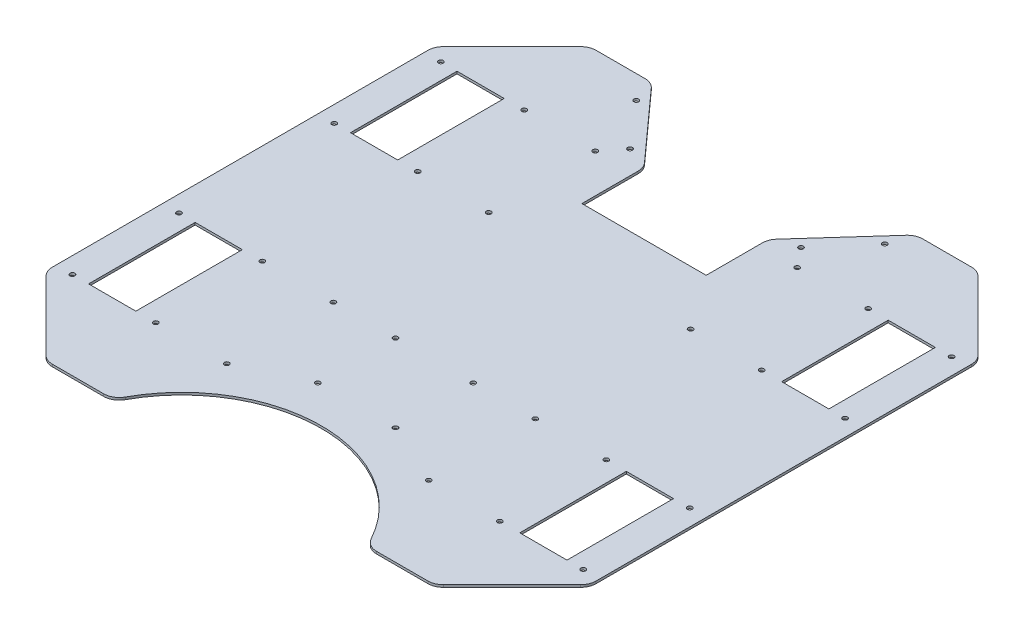
SolidWorks part; units mm, degrees
material "PMMA"
ref_plane "前视基准面" through (0, 0, 0) normal (0, 0, 1) x (1, 0, 0)
ref_plane "上视基准面" through (0, 0, 0) normal (0, 1, 0) x (1, 0, 0)
ref_plane "右视基准面" through (0, 0, 0) normal (1, 0, 0) x (0, 0, -1)
other "Configuration Table"
sketch "草图1" plane through (0, 0, 0) normal (0, 1, 0) x (1, 0, 0)
  line L0 (-125, 175) -> (-175, 125)
  line L1 (125, -175) -> (81.7103, -175)
  line L2 (175, -125) -> (175, 125)
  line L3 (125, 175) -> (85, 175)
  line L4 (-175, -125) -> (-175, 125)
  line L5 (-85, 175) -> (-40, 125)
  line L7 (125, 175) -> (175, 125)
  line L8 (175, -125) -> (125, -175)
  line L9 (-125, -175) -> (-175, -125)
  line L10 (40, 125) -> (85, 175)
  line L11 (-85, 175) -> (-125, 175)
  line L12 (40, 125) -> (40, 85)
  line L13 (40, 85) -> (-40, 85)
  line L14 (-40, 85) -> (-40, 125)
  line L15 (-153.994, 50) -> (-123.594, 50)
  line L16 (-123.594, 50) -> (-123.594, 118.58)
  line L17 (-123.594, 118.58) -> (-153.994, 118.58)
  line L18 (-153.994, 118.58) -> (-153.994, 50)
  line L19 (123.594, 50) -> (153.994, 50)
  line L20 (153.994, 50) -> (153.994, 118.58)
  line L21 (153.994, 118.58) -> (123.594, 118.58)
  line L22 (123.594, 118.58) -> (123.594, 50)
  line L23 (-175, 0) -> (175, 0) construction
  line L24 (-123.594, -118.58) -> (-153.994, -118.58)
  line L25 (-123.594, -50) -> (-123.594, -118.58)
  line L26 (-153.994, -50) -> (-123.594, -50)
  line L27 (-153.994, -118.58) -> (-153.994, -50)
  line L28 (153.994, -118.58) -> (123.594, -118.58)
  line L29 (153.994, -50) -> (153.994, -118.58)
  line L30 (123.594, -50) -> (153.994, -50)
  line L31 (123.594, -118.58) -> (123.594, -50)
  line L32 (-81.7103, -175) -> (-125, -175)
  line L33 (-80, 160) -> (-55, 131) construction
  circle A0 centre (-55, 131) radius 1.55
  circle A1 centre (-80, 160) radius 1.55
  circle A2 centre (55, 131) radius 1.55
  circle A3 centre (80, 160) radius 1.55
  circle A4 centre (-65, 118.58) radius 1.55
  circle A5 centre (-65, 50) radius 1.55
  circle A6 centre (-110.72, 50) radius 1.55
  circle A7 centre (-110.72, 118.58) radius 1.55
  circle A12 centre (-164.434, 118.58) radius 1.55
  circle A13 centre (-164.434, 50) radius 1.55
  circle A14 centre (-65, -118.58) radius 1.55
  circle A15 centre (-65, -50) radius 1.55
  circle A16 centre (-110.72, -50) radius 1.55
  circle A17 centre (-110.72, -118.58) radius 1.55
  circle A18 centre (-164.434, -50) radius 1.55
  circle A19 centre (-164.434, -118.58) radius 1.55
  circle A20 centre (65, 50) radius 1.55
  circle A21 centre (110.72, 50) radius 1.55
  circle A22 centre (110.72, 118.58) radius 1.55
  circle A23 centre (65, 118.58) radius 1.55
  circle A24 centre (164.434, 118.58) radius 1.55
  circle A25 centre (164.434, 50) radius 1.55
  circle A26 centre (164.434, -118.58) radius 1.55
  circle A27 centre (164.434, -50) radius 1.55
  circle A28 centre (110.72, -50) radius 1.55
  circle A29 centre (110.72, -118.58) radius 1.55
  circle A30 centre (65, -118.58) radius 1.55
  circle A31 centre (65, -50) radius 1.55
  arc A32 (-81.7103, -175) -> (81.7103, -175) centre (0, -212.7283) cw
  circle A33 centre (25, -50) radius 1.55
  circle A34 centre (25, -100) radius 1.55
  circle A35 centre (-25, -50) radius 1.55
  circle A36 centre (-25, -100) radius 1.55
  point P0 (0, 0)
  point P1 (-85, 175)
  point P2 (85, 175)
  point P3 (40, 125)
  point P4 (-40, 125)
  point P6 (125, 175)
  point P8 (175, 125)
  point P10 (175, -125)
  point P11 (125, -175)
  point P12 (-125, -175)
  point P13 (-175, -125)
  point P24 (-80, 160)
  point P25 (-55, 131)
  point P26 (55, 131)
  point P27 (80, 160)
  point P36 (-164.434, 118.58)
  point P37 (-164.434, 50)
  point P38 (-153.994, 118.58)
  point P39 (-123.594, 50)
  point P40 (-110.72, 118.58)
  point P41 (-110.72, 50)
  point P42 (-65, 118.58)
  point P43 (-65, 50)
  point P47 (-123.594, 118.58)
  point P53 (-153.994, 50)
  point P66 (-40, 85)
  point P67 (40, 85)
  point P70 (110.72, 50)
  point P71 (65, 50)
  point P72 (123.594, 50)
  point P73 (153.994, 50)
  point P74 (164.434, 50)
  point P75 (65, 118.58)
  point P76 (110.72, 118.58)
  point P77 (123.594, 118.58)
  point P78 (153.994, 118.58)
  point P81 (164.434, 118.58)
  point P85 (-65, -118.58)
  point P88 (-65, -50)
  point P91 (-110.72, -50)
  point P94 (-110.72, -118.58)
  point P101 (-164.434, -50)
  point P104 (-164.434, -118.58)
  point P118 (164.434, -118.58)
  point P121 (164.434, -50)
  point P128 (110.72, -50)
  point P131 (110.72, -118.58)
  point P134 (65, -118.58)
  point P137 (65, -50)
  point P149 (0, 0)
  point P150 (0, 0)
  point P151 (0, 0)
  point P152 (-989.1218, 614.5739)
  point P153 (0, 0)
  point P154 (0, 0)
  dimension "D29" = 3.1
  dimension "D30" = 3.1
  dimension "D31" = 3.1
  dimension "D32" = 3.1
  dimension "D40" = 3.1
  dimension "D41" = 3.1
  dimension "D42" = 3.1
  dimension "D43" = 3.1
  dimension "D44" = 3.1
  dimension "D45" = 3.1
  dimension "D46" = 3.1
  dimension "D47" = 3.1
  dimension "D48" = 3.1
  dimension "D49" = 3.1
  dimension "D60" = 3.1
  dimension "D61" = 3.1
  dimension "D62" = 43.2897
  dimension "D63" = 90
  dimension "D67" = 3.1
  dimension "D68" = 3.1
  dimension "D69" = 3.1
  dimension "D70" = 3.1
  dimension "D1" = 175
  dimension "D2" = 175
  dimension "D3" = 125
  dimension "D4" = 125
  dimension "D5" = 125
  dimension "D6" = 125
  dimension "D7" = 125
  dimension "D8" = 125
  dimension "D9" = 125
  dimension "D10" = 125
  dimension "D11" = 175
  dimension "D12" = 175
  dimension "D13" = 40
  dimension "D14" = 40
  dimension "D15" = 85
  dimension "D16" = 85
  dimension "D17" = 125
  dimension "D18" = 125
  dimension "D19" = 40
  dimension "D20" = 45
  dimension "D21" = 160
  dimension "D22" = 160
  dimension "D23" = 80
  dimension "D24" = 80
  dimension "D25" = 55
  dimension "D26" = 131
  dimension "D27" = 55
  dimension "D28" = 131
  dimension "D33" = 50
  dimension "D34" = 118.58
  dimension "D35" = 65
  dimension "D36" = 45.72
  dimension "D37" = 12.874
  dimension "D38" = 30.4
  dimension "D39" = 10.44
  dimension "D50" = 40
  dimension "D51" = 40
  dimension "D52" = 85
  dimension "D53" = 85
  dimension "D54" = 138.013
  dimension "D55" = 65
  dimension "D56" = 45.72
  dimension "D57" = 12.874
  dimension "D58" = 30.4
  dimension "D59" = 10.44
  dimension "D64" = 0
  dimension "D65" = 25
  dimension "D66" = 25
  dimension "D71" = 50
  dimension "D72" = 50
extrude "凸台-拉伸1" add sketch "草图1" along normal blind 1.5 contours A1 | A0 | L8 L1 A32 L32 L9 L4 L0 L11 L5 L14 L13 L12 L10 L3 L7 L2 | A5 | A3 | A2 | A4 | A7 | A12 | L16 L17 L18 L15 | A6 | L21 L22 L19 L20 | A13 | A16 | A17 | A14 | A15 | A18 | A19 | L25 L24 L27 L26 | A20 | A21 | A22 | A23 | A24 | A25 | A28 | A26 | A27 | L28 L31 L30 L29 | A30 | A31 | A29 | A35 | A36 | A33 | A34
fillet "圆角1" radius 10 1 edges at (-40, 0.75, -125)
fillet "圆角2" radius 10 1 edges at (40, 0.75, -125)
fillet "圆角3" radius 10 12 edges at (-85, 0.75, -175) (85, 0.75, -175) (125, 0.75, -175) (175, 0.75, -125) (175, 0.75, 125) (125, 0.75, 175) (81.7103, 0.75, 175) (-81.7103, 0.75, 175) (-125, 0.75, 175) (-175, 0.75, 125) (-175, 0.75, -125) (-125, 0.75, -175)
